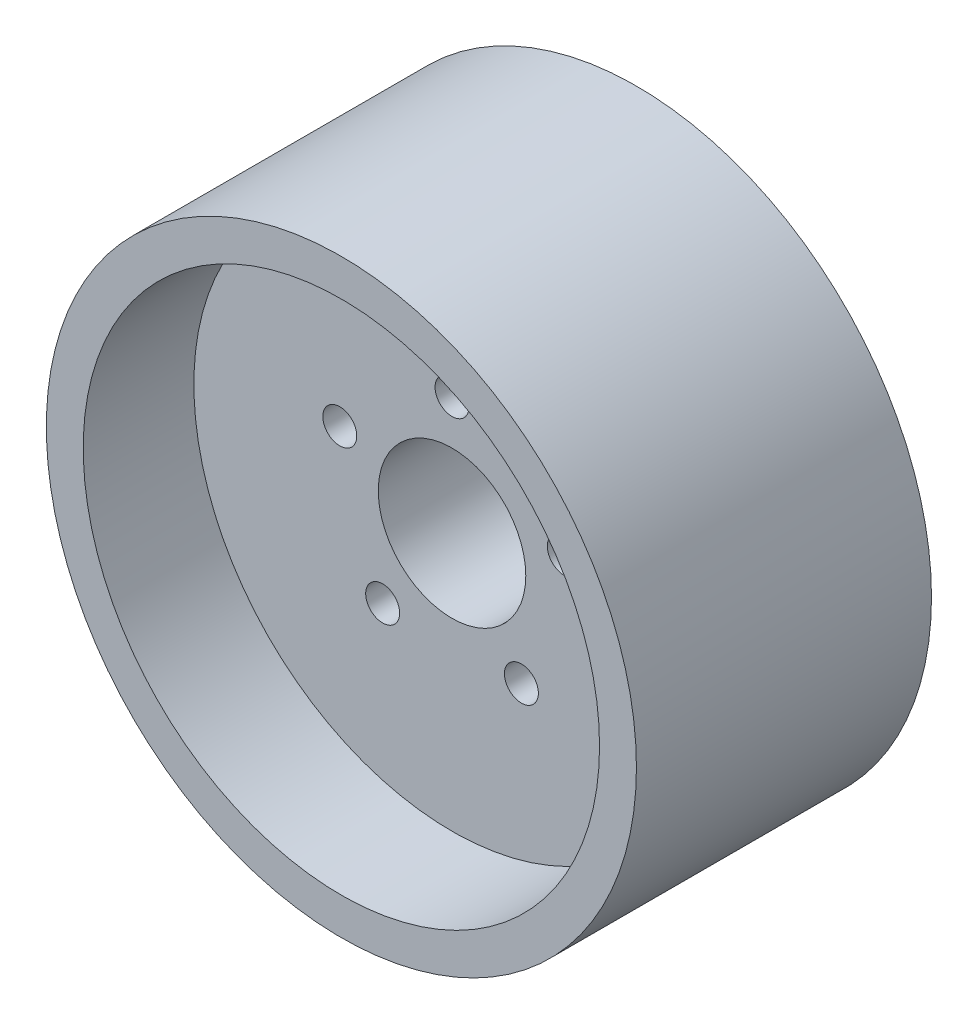
SolidWorks part; units mm, degrees
ref_plane "Front Plane" through (0, 0, 0) normal (0, 0, 1) x (1, 0, 0)
ref_plane "Top Plane" through (0, 0, 0) normal (0, 1, 0) x (1, 0, 0)
ref_plane "Right Plane" through (0, 0, 0) normal (1, 0, 0) x (0, 0, -1)
sketch "Sketch1" plane through (0, 0, 0) normal (0, 0, 1) x (1, 0, 0)
  line L0 (0, 0) -> (0, 20.32) construction
  line L1 (0, 0) -> (19.3255, 6.2792) construction
  line L2 (0, 0) -> (11.9438, -16.4392) construction
  line L3 (0, 0) -> (-11.9438, -16.4392) construction
  line L4 (0, 0) -> (-19.3255, 6.2792) construction
  circle A0 centre (0, 0) radius 50.8
  circle A1 centre (0, 0) radius 12.7
  circle A2 centre (0, 20.32) radius 2.921
  circle A3 centre (19.3255, 6.2792) radius 2.921
  circle A4 centre (11.9438, -16.4392) radius 2.921
  circle A5 centre (-11.9438, -16.4392) radius 2.921
  circle A6 centre (-19.3255, 6.2792) radius 2.921
  point P17 (0, 0)
  dimension "D1" = 25.4
  dimension "D2" = 101.6
  dimension "D3" = 5.842
  dimension "D5" = 20.32
  dimension "D4" = 5
extrude "Boss-Extrude2" add sketch "Sketch1" along normal blind 25.4 and the other way blind 25.4
sketch "Sketch2" plane through (0, 0, 25.4) normal (0, 0, 1) x (1, 0, 0)
  circle A0 centre (0, 0) radius 44.45
  dimension "D1" = 88.9
extrude "Cut-Extrude1" cut sketch "Sketch2" against normal blind 19.05
ref_plane "Plane1" through (0, 0, 0) normal (0, 0, 1) x (1, 0, 0)
ref_plane "Plane2" through (0, 0, -25.4) normal (0, 0, -1) x (-1, 0, 0)
